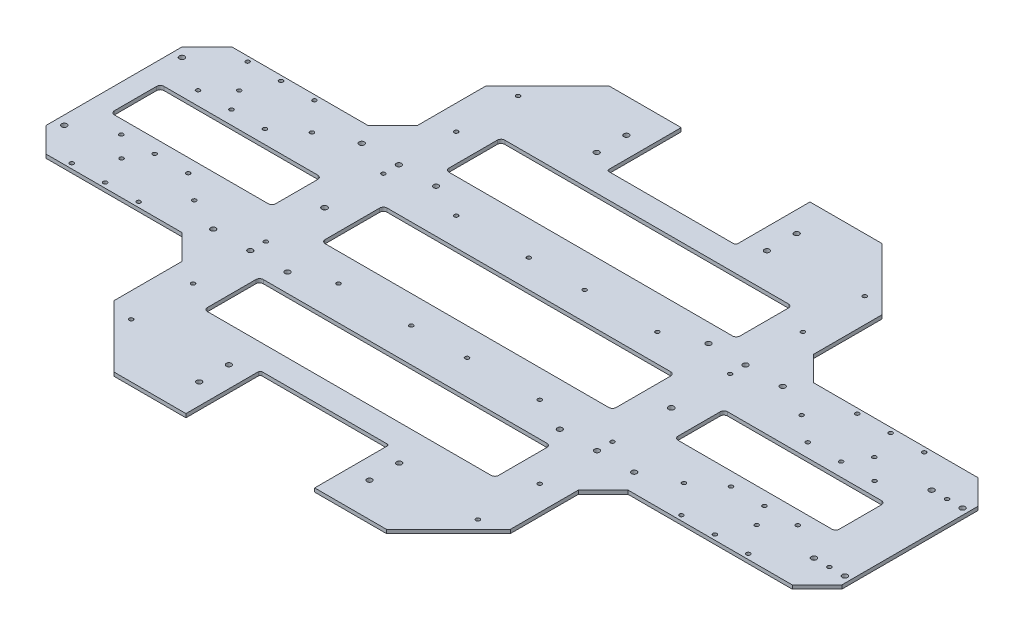
SolidWorks part; units mm, degrees
material "6061-O (SS)"
ref_plane "前视基准面" through (0, 0, 0) normal (0, 0, 1) x (1, 0, 0)
ref_plane "上视基准面" through (0, 0, 0) normal (0, 1, 0) x (1, 0, 0)
ref_plane "右视基准面" through (0, 0, 0) normal (1, 0, 0) x (0, 0, -1)
sketch "草图1" plane through (0, 0, 0) normal (0, 1, 0) x (1, 0, 0)
  line L0 (0, 0) -> (160, -38.7097) construction
  line L1 (-260, 200) -> (260, 200) construction
  line L2 (-260, 200) -> (-260, -200) construction
  line L3 (-260, -200) -> (260, -200) construction
  line L4 (260, 200) -> (260, -200) construction
  line L5 (-260, 200) -> (-160, 123.0769) construction
  line L6 (-260, -200) -> (-160, -123.0769) construction
  line L7 (-310, -75) -> (-160, -75)
  line L8 (-310, -75) -> (-310, 75)
  line L9 (-310, 75) -> (-160, 75)
  line L10 (310, -75) -> (310, 75)
  line L11 (-310, -75) -> (160, 38.7097) construction
  line L12 (-310, 75) -> (-160, 38.7097) construction
  line L13 (-160, -200) -> (160, -200)
  line L14 (-160, -200) -> (-160, -75)
  line L15 (-160, 200) -> (160, 200)
  line L16 (160, -200) -> (160, -75)
  line L17 (-60, -75) -> (0, 0) construction
  line L18 (0, 0) -> (60, -75) construction
  line L19 (-160, 75) -> (-160, 200)
  line L22 (160, 75) -> (310, 75)
  line L24 (97.5, 75) -> (260, 200) construction
  line L25 (160, 75) -> (160, 200)
  line L26 (260, 62.9032) -> (310, 75) construction
  line L27 (260, -62.9032) -> (310, -75) construction
  line L28 (160, -75) -> (310, -75)
  line L29 (160, -123.0769) -> (260, -200) construction
  point P0 (0, 0)
  point P6 (0, 0)
  point P11 (0, 0)
  dimension "D1" = 520
  dimension "D2" = 400
  dimension "D3" = 50
  dimension "D4" = 125
  dimension "D5" = 100
extrude "凸台-拉伸1" add sketch "草图1" along normal blind 3
chamfer "倒角1" distance 20 angle 45 8 edges at (-160, 1.5, -75) (-310, 1.5, -75) (-310, 1.5, 75) (-160, 1.5, 75) (160, 1.5, 75) (160, 1.5, -75) (310, 1.5, 75) (310, 1.5, -75)
chamfer "倒角2" distance 50 angle 45 4 edges at (160, 1.5, 200) (-160, 1.5, 200) (160, 1.5, -200) (-160, 1.5, -200)
sketch "草图2" plane through (0, 0, 0) normal (0, -1, 0) x (-1, 0, 0)
  line L1 (52, -140) -> (-52, -140)
  line L2 (52, -140) -> (52, -233.0888)
  line L3 (52, -233.0888) -> (-52, -233.0888)
  line L4 (-52, -140) -> (-52, -233.0888)
  line L6 (0, 0) -> (119.8246, 0) construction
  line L7 (-52, 140) -> (-52, 233.0888)
  line L8 (52, 233.0888) -> (-52, 233.0888)
  line L9 (52, 140) -> (52, 233.0888)
  line L10 (52, 140) -> (-52, 140)
  line L11 (160, -95) -> (160, -150) construction
  line L12 (-160, -150) -> (-160, -95) construction
  dimension "D1" = 108
  dimension "D2" = 108
extrude "切除-拉伸1" cut sketch "草图2" against normal blind 40
fillet "圆角1" radius 1.5 4 edges at (-52, 1.5, -140) (52, 1.5, -140) (52, 1.5, 140) (-52, 1.5, 140)
sketch "草图3" plane through (0, 0, 0) normal (0, -1, 0) x (1, 0, 0)
  circle A0 centre (-68.75, 172.5) radius 2.1
  circle A1 centre (-68.75, 148.5) radius 2.1
  circle A2 centre (68.75, 172.5) radius 2.1
  circle A3 centre (68.75, 148.5) radius 2.1
  circle A4 centre (-68.75, -148.5) radius 2.1
  circle A5 centre (-68.75, -172.5) radius 2.1
  circle A6 centre (68.75, -148.5) radius 2.1
  circle A7 centre (68.75, -172.5) radius 2.1
extrude "切除-拉伸2" cut sketch "草图3" against normal blind 80
sketch "草图4" plane through (0, 0, 0) normal (0, -1, 0) x (1, 0, 0)
  line L0 (0, 0) -> (124.2092, 0) construction
  line L1 (0, 0) -> (0, 63.2758) construction
  circle A0 centre (273.2002, 71) radius 1.6
  circle A1 centre (273.2002, 30.9984) radius 1.6
  circle A2 centre (246.2002, 71) radius 1.6
  circle A3 centre (219.2002, 71) radius 1.6
  circle A4 centre (246.2002, 30.9984) radius 1.6
  circle A5 centre (219.2002, 30.9984) radius 1.6
  circle A6 centre (110, 60) radius 2.1
  circle A7 centre (140, 60) radius 2.1
  circle A8 centre (170, 60) radius 2.1
  circle A9 centre (170, -60) radius 2.1
  circle A10 centre (140, -60) radius 2.1
  circle A11 centre (110, -60) radius 2.1
  circle A12 centre (219.2002, -30.9984) radius 1.6
  circle A13 centre (246.2002, -30.9984) radius 1.6
  circle A14 centre (219.2002, -71) radius 1.6
  circle A15 centre (246.2002, -71) radius 1.6
  circle A16 centre (273.2002, -30.9984) radius 1.6
  circle A17 centre (273.2002, -71) radius 1.6
  circle A18 centre (-273.2002, -71) radius 1.6
  circle A19 centre (-273.2002, -30.9984) radius 1.6
  circle A20 centre (-246.2002, -71) radius 1.6
  circle A21 centre (-219.2002, -71) radius 1.6
  circle A22 centre (-246.2002, -30.9984) radius 1.6
  circle A23 centre (-219.2002, -30.9984) radius 1.6
  circle A24 centre (-110, -60) radius 2.1
  circle A25 centre (-140, -60) radius 2.1
  circle A26 centre (-170, -60) radius 2.1
  circle A27 centre (-170, 60) radius 2.1
  circle A28 centre (-140, 60) radius 2.1
  circle A29 centre (-110, 60) radius 2.1
  circle A30 centre (-219.2002, 30.9984) radius 1.6
  circle A31 centre (-246.2002, 30.9984) radius 1.6
  circle A32 centre (-219.2002, 71) radius 1.6
  circle A33 centre (-246.2002, 71) radius 1.6
  circle A34 centre (-273.2002, 30.9984) radius 1.6
  circle A35 centre (-273.2002, 71) radius 1.6
extrude "切除-拉伸3" cut sketch "草图4" against normal blind 29
sketch "草图5" plane through (0, 0, 0) normal (0, -1, 0) x (1, 0, 0)
  line L0 (310, 55) -> (290, 75) construction
  line L1 (310, 55) -> (310, -55) construction
  line L2 (290, -75) -> (310, -55) construction
  line L3 (310, 55) -> (290, 75)
  line L4 (310, 55) -> (310, -55)
  line L5 (290, -75) -> (310, -55)
  line L6 (290, -75) -> (312.7002, -75)
  line L7 (312.7002, -75) -> (332.7002, -55)
  line L9 (332.7002, -55) -> (332.7002, 55)
  line L10 (332.7002, 55) -> (312.7002, 75)
  line L11 (312.7002, 75) -> (290, 75)
extrude "凸台-拉伸2" add sketch "草图5" against normal blind 3
sketch "草图6" plane through (0, 0, 0) normal (0, -1, 0) x (1, 0, 0)
  circle A0 centre (302.7002, 47.5) radius 2.15
  circle A1 centre (327.7002, 47.5) radius 2.15
  circle A2 centre (327.7002, -47.5) radius 2.15
  circle A3 centre (302.7002, -47.5) radius 2.15
  dimension "D1" = 4.3
extrude "切除-拉伸4" cut sketch "草图6" against normal blind 3
sketch "草图7" plane through (0, 0, 0) normal (0, -1, 0) x (1, 0, 0)
  line L0 (180, 75) -> (312.7002, 75) construction
  line L1 (289.7002, -20) -> (165.5, -20)
  line L2 (292.7002, -17) -> (292.7002, 17)
  line L3 (289.7002, 20) -> (165.5, 20)
  line L4 (162.5, -17) -> (162.5, 17)
  line L5 (114.5, -25) -> (-114.5, -25)
  line L6 (117.5, -22) -> (117.5, 22)
  line L7 (114.5, 25) -> (-114.5, 25)
  line L8 (-117.5, -22) -> (-117.5, 22)
  line L9 (114.5, -120) -> (-114.5, -120)
  line L10 (117.5, -117) -> (117.5, -78)
  line L11 (114.5, -75) -> (-114.5, -75)
  line L12 (-117.5, -117) -> (-117.5, -78)
  line L13 (312.7002, -75) -> (180, -75) construction
  line L14 (307.7002, -40) -> (307.7002, 40) construction
  line L15 (147.5, -40) -> (147.5, 40) construction
  line L16 (-132.5, -40) -> (-132.5, 40) construction
  line L17 (132.5, 40) -> (-132.5, 40) construction
  line L18 (132.5, -40) -> (132.5, 40) construction
  line L19 (132.5, -40) -> (-132.5, -40) construction
  line L20 (132.5, -55) -> (-132.5, -55) construction
  line L21 (132.5, -55) -> (132.5, -295) construction
  line L22 (-132.5, -55) -> (-132.5, -295) construction
  line L23 (45.4531, 0) -> (0, 0) construction
  line L24 (0, 0) -> (0, 77.4247) construction
  line L25 (-162.5, -17) -> (-162.5, 17)
  line L26 (-289.7002, 20) -> (-165.5, 20)
  line L27 (-292.7002, -17) -> (-292.7002, 17)
  line L28 (-289.7002, -20) -> (-165.5, -20)
  line L29 (-117.5, 117) -> (-117.5, 78)
  line L30 (114.5, 75) -> (-114.5, 75)
  line L31 (117.5, 117) -> (117.5, 78)
  line L32 (114.5, 120) -> (-114.5, 120)
  arc A0 (289.7002, -20) -> (292.7002, -17) centre (289.7002, -17) ccw
  arc A1 (292.7002, 17) -> (289.7002, 20) centre (289.7002, 17) ccw
  arc A2 (165.5, -20) -> (162.5, -17) centre (165.5, -17) cw
  arc A3 (165.5, 20) -> (162.5, 17) centre (165.5, 17) ccw
  arc A4 (114.5, -120) -> (117.5, -117) centre (114.5, -117) ccw
  arc A5 (-114.5, -120) -> (-117.5, -117) centre (-114.5, -117) cw
  arc A6 (-114.5, -75) -> (-117.5, -78) centre (-114.5, -78) ccw
  arc A7 (117.5, -78) -> (114.5, -75) centre (114.5, -78) ccw
  arc A8 (114.5, -25) -> (117.5, -22) centre (114.5, -22) ccw
  arc A9 (117.5, 22) -> (114.5, 25) centre (114.5, 22) ccw
  arc A10 (-114.5, -25) -> (-117.5, -22) centre (-114.5, -22) cw
  arc A11 (-114.5, 25) -> (-117.5, 22) centre (-114.5, 22) ccw
  arc A12 (-165.5, 20) -> (-162.5, 17) centre (-165.5, 17) cw
  arc A13 (-165.5, -20) -> (-162.5, -17) centre (-165.5, -17) ccw
  arc A14 (-292.7002, 17) -> (-289.7002, 20) centre (-289.7002, 17) cw
  arc A15 (-289.7002, -20) -> (-292.7002, -17) centre (-289.7002, -17) cw
  arc A16 (117.5, 78) -> (114.5, 75) centre (114.5, 78) cw
  arc A17 (-114.5, 75) -> (-117.5, 78) centre (-114.5, 78) cw
  arc A18 (-114.5, 120) -> (-117.5, 117) centre (-114.5, 117) ccw
  arc A19 (114.5, 120) -> (117.5, 117) centre (114.5, 117) cw
  point P46 (-117.5, -120)
  point P49 (-117.5, -75)
  dimension "D13" = 3
  dimension "D1" = 55
  dimension "D2" = 55
  dimension "D3" = 15
  dimension "D4" = 15
  dimension "D5" = 15
  dimension "D6" = 15
  dimension "D7" = 15
  dimension "D8" = 15
  dimension "D9" = 20
  dimension "D10" = 15
  dimension "D11" = 15
  dimension "D12" = 45
extrude "切除-拉伸5" cut sketch "草图7" against normal blind 15
sketch "草图8" plane through (0, 0, 0) normal (0, -1, 0) x (1, 0, 0)
  line L0 (40.5777, 0) -> (-40.5777, 0) construction
  line L1 (0, 0) -> (0, 30.149) construction
  circle A0 centre (140, 0) radius 2.2407 construction
  circle A1 centre (140, 156.23) radius 1.6 construction
  circle A2 centre (140, 106.23) radius 1.6 construction
  circle A3 centre (22.54, 47.5) radius 1.6 construction
  circle A4 centre (81.27, 47.5) radius 1.6 construction
  circle A5 centre (140, 47.5) radius 1.6 construction
  circle A6 centre (197.7368, 47.5) radius 1.6 construction
  circle A7 centre (256.4668, 47.5) radius 1.6 construction
  circle A8 centre (315.2002, 47.5) radius 1.6 construction
  circle A9 centre (140, 0) radius 2.2407
  circle A10 centre (140, 156.23) radius 1.6
  circle A11 centre (140, 106.23) radius 1.6
  circle A12 centre (22.54, 47.5) radius 1.6
  circle A13 centre (81.27, 47.5) radius 1.6
  circle A14 centre (140, 47.5) radius 1.6
  circle A15 centre (197.7368, 47.5) radius 1.6
  circle A16 centre (256.4668, 47.5) radius 1.6
  circle A17 centre (315.2002, 47.5) radius 1.6
  circle A18 centre (315.2002, -47.5) radius 1.6
  circle A19 centre (256.4668, -47.5) radius 1.6
  circle A20 centre (197.7368, -47.5) radius 1.6
  circle A21 centre (140, -47.5) radius 1.6
  circle A22 centre (81.27, -47.5) radius 1.6
  circle A23 centre (22.54, -47.5) radius 1.6
  circle A24 centre (140, -106.23) radius 1.6
  circle A25 centre (140, -156.23) radius 1.6
  circle A26 centre (-140, -156.23) radius 1.6
  circle A27 centre (-140, -106.23) radius 1.6
  circle A28 centre (-22.54, -47.5) radius 1.6
  circle A29 centre (-81.27, -47.5) radius 1.6
  circle A30 centre (-140, -47.5) radius 1.6
  circle A31 centre (-197.7368, -47.5) radius 1.6
  circle A32 centre (-256.4668, -47.5) radius 1.6
  circle A33 centre (-315.2002, -47.5) radius 1.6
  circle A34 centre (-315.2002, 47.5) radius 1.6
  circle A35 centre (-256.4668, 47.5) radius 1.6
  circle A36 centre (-197.7368, 47.5) radius 1.6
  circle A37 centre (-140, 47.5) radius 1.6
  circle A38 centre (-81.27, 47.5) radius 1.6
  circle A39 centre (-22.54, 47.5) radius 1.6
  circle A40 centre (-140, 106.23) radius 1.6
  circle A41 centre (-140, 156.23) radius 1.6
  circle A42 centre (-140, 0) radius 2.2407
  circle A43 centre (-302.7002, -47.5) radius 2.15 construction
  circle A44 centre (-302.7002, 47.5) radius 2.15 construction
  circle A45 centre (-302.7002, -47.5) radius 2.15
  circle A46 centre (-302.7002, 47.5) radius 2.15
extrude "切除-拉伸6" cut sketch "草图8" against normal blind 15
